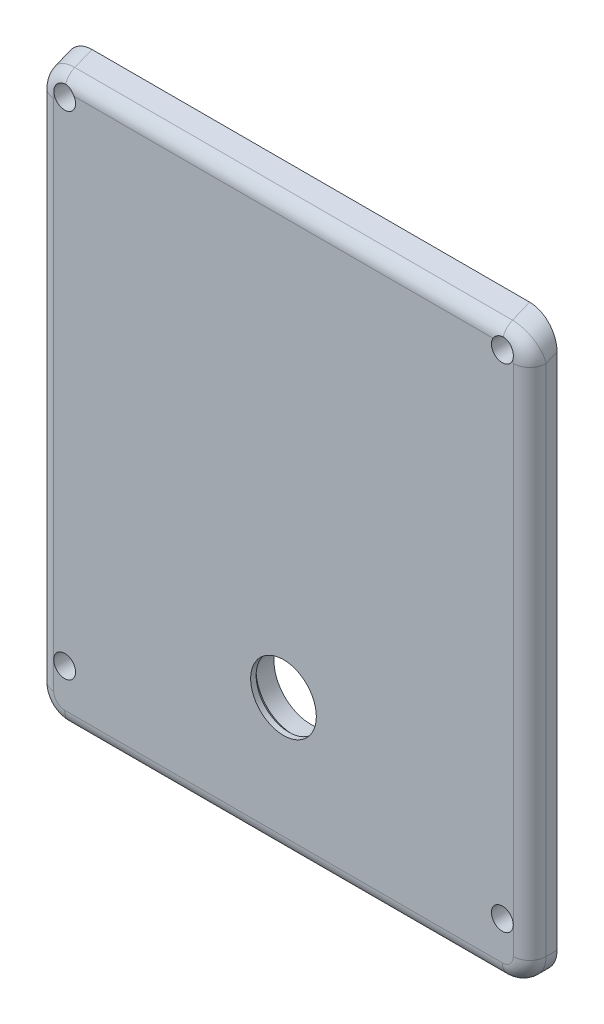
SolidWorks part; units mm, degrees
ref_plane "Front Plane" through (0, 0, 0) normal (0, 0, 1) x (1, 0, 0)
ref_plane "Top Plane" through (0, 0, 0) normal (0, 1, 0) x (1, 0, 0)
ref_plane "Right Plane" through (0, 0, 0) normal (1, 0, 0) x (0, 0, -1)
sketch "Sketch1" plane through (0, 0, 0) normal (1, 0, 0) x (0, 0, -1)
  line L0 (28.5, -55) -> (-16.5, 55)
  line L1 (-28.5, 55) -> (28.5, 55)
  line L2 (-28.5, 55) -> (-28.5, -55)
  line L3 (-28.5, -55) -> (28.5, -55)
  line L4 (28.5, 55) -> (28.5, -55)
  line L5 (-28.5, 55) -> (28.5, -55) construction
  line L6 (-28.5, -55) -> (28.5, 55) construction
  line L7 (-16.5, 55) -> (-33.5, 48.0455)
  line L8 (-28.5, -55) -> (-33.5, -55)
  line L9 (-33.5, -55) -> (-33.5, 48.0455)
  point P0 (0, 0)
  dimension "D1" = 110
  dimension "D2" = 57
  dimension "D3" = 45
  dimension "D4" = 5
extrude "Boss-Extrude1" add sketch "Sketch1" along normal mid plane 90 contours L9 L8 L2 L7 region at (0, -2.9642, 30.9918)
sketch "Sketch2" plane through (0, 0, 0) normal (0, 0, 1) x (1, 0, 0)
  line L1 (-40, 45) -> (40, 45) construction
  line L2 (-40, 45) -> (-40, -45) construction
  line L3 (-40, -45) -> (40, -45) construction
  line L4 (40, 45) -> (40, -45) construction
  line L5 (-40, 45) -> (40, -45) construction
  line L6 (-40, -45) -> (40, 45) construction
  circle A0 centre (-40, -45) radius 2
  circle A1 centre (40, -45) radius 2
  circle A2 centre (40, 45) radius 2
  circle A3 centre (-40, 45) radius 2
  point P0 (0, 0)
  dimension "D3" = 4
  dimension "D4" = 4
  dimension "D5" = 4
  dimension "D6" = 4
  dimension "D1" = 90
  dimension "D2" = 80
extrude "Cut-Extrude1" cut sketch "Sketch2" along normal blind 90
fillet "Fillet1" radius 5 4 edges at (-45, -55, 31) (45, -55, 31) (45, 49.0682, 31) (-45, 49.0682, 31)
fillet "Fillet2" radius 3 8 edges at (43.5355, -53.5355, 33.5) (0, -55, 33.5) (-43.5355, -53.5355, 33.5) (-45, -3.6784, 33.5) (-43.5355, 46.4632, 33.5) (0, 48.0455, 33.5) (43.5355, 46.4632, 33.5) (45, -3.6784, 33.5)
sketch "Sketch3" plane through (0, 0, 0) normal (0, 0, 1) x (1, 0, 0)
  circle A0 centre (0, -30) radius 6
  dimension "D1" = 12
  dimension "D2" = 30
extrude "Cut-Extrude3" cut sketch "Sketch3" along normal through all
sketch "Sketch4" plane through (0, 0, 33.5) normal (0, 0, 1) x (1, 0, 0)
  circle A0 centre (0, -30) radius 6.75
  dimension "D1" = 13.5
extrude "Cut-Extrude4" cut sketch "Sketch4" against normal blind 5 from offset 1 offset against normal yes
chamfer "Chamfer1" distance 0.75 angle 45 1 edges at (6.75, -30, 32.5)
